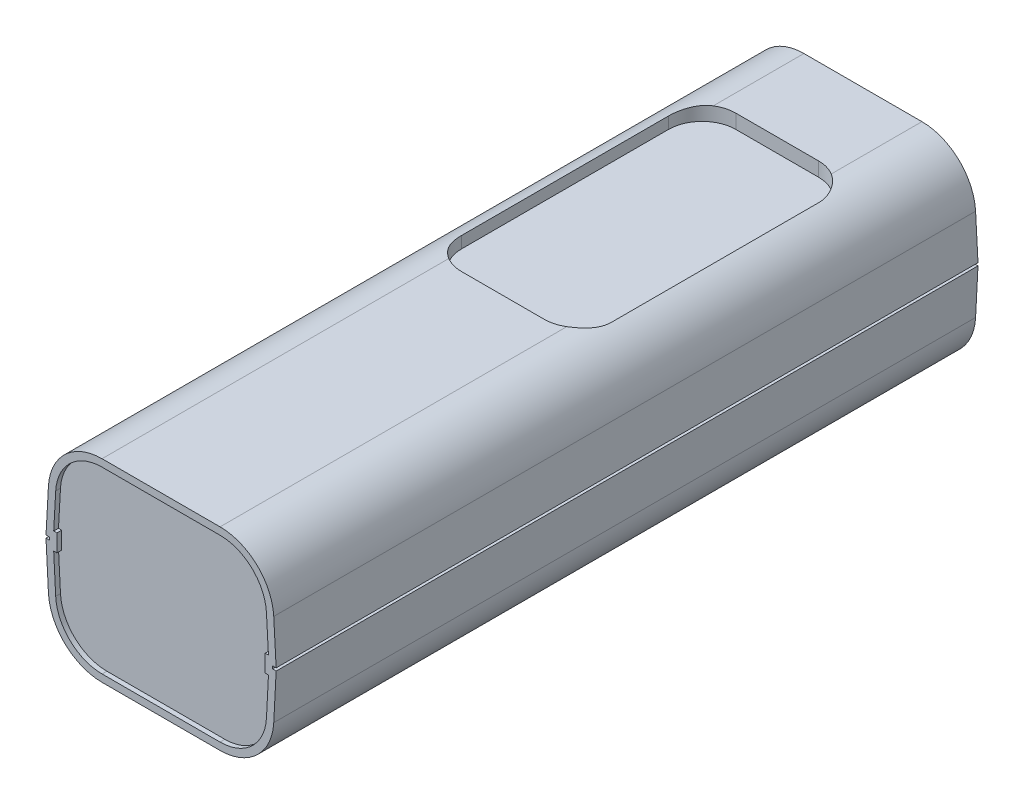
SolidWorks part; units mm, degrees
material "ABS"
ref_plane "Front Plane" through (0, 0, 0) normal (0, 0, 1) x (1, 0, 0)
ref_plane "Top Plane" through (0, 0, 0) normal (0, 1, 0) x (1, 0, 0)
ref_plane "Right Plane" through (0, 0, 0) normal (1, 0, 0) x (0, 0, -1)
sketch "main_features_sketch" plane through (0, 0, 0) normal (0, 0, 1) x (1, 0, 0)
  line L1 (12.9462, 21.25) -> (-12.9462, 21.25)
  line L3 (12.9462, -21.25) -> (-12.9462, -21.25)
  line L5 (0, -21.25) -> (0, 21.25) construction
  line L6 (25.25, 0) -> (-25.25, 0) construction
  line L7 (-25.25, 0) -> (-24.722, -10.0752)
  line L8 (-24.7199, 10.1141) -> (-25.25, 0.6)
  line L9 (-25.25, 0) -> (-24.45, 0)
  line L10 (-24.45, 0) -> (-24.45, 0.6)
  line L11 (-24.45, 0.6) -> (-25.25, 0.6)
  line L12 (25.25, 0) -> (24.45, 0)
  line L13 (24.45, 0.6) -> (25.25, 0.6)
  line L14 (24.45, 0) -> (24.45, 0.6)
  line L15 (24.7199, 10.1141) -> (25.25, 0.6)
  line L16 (25.25, 0) -> (24.722, -10.0752)
  line L17 (-12.9462, 9.4581) -> (0, 0) construction
  line L18 (0, 0) -> (-12.9462, -9.4581) construction
  line L19 (12.9462, 19.65) -> (-12.9462, 19.65)
  line L20 (23.1224, 10.0251) -> (23.5584, 2.2)
  line L21 (22.85, 2.2) -> (23.5584, 2.2)
  line L22 (22.85, -1.6) -> (22.85, 2.2)
  line L23 (23.564, -1.6) -> (22.85, -1.6)
  line L24 (23.564, -1.6) -> (23.1242, -9.9915)
  line L25 (12.9462, -19.65) -> (-12.9462, -19.65)
  line L26 (-23.564, -1.6) -> (-23.1242, -9.9915)
  line L27 (-23.564, -1.6) -> (-22.85, -1.6)
  line L28 (-22.85, -1.6) -> (-22.85, 2.2)
  line L29 (-22.85, 2.2) -> (-23.5584, 2.2)
  line L30 (-23.1224, 10.0251) -> (-23.5584, 2.2)
  arc A4 (-24.7199, 10.1141) -> (-12.9462, 21.25) centre (-12.9462, 9.4581) cw
  arc A5 (-24.722, -10.0752) -> (-12.9462, -21.25) centre (-12.9462, -9.4581) ccw
  arc A6 (24.7199, 10.1141) -> (12.9462, 21.25) centre (12.9462, 9.4581) ccw
  arc A7 (24.722, -10.0752) -> (12.9462, -21.25) centre (12.9462, -9.4581) cw
  arc A8 (-23.1224, 10.0251) -> (-12.9462, 19.65) centre (-12.9462, 9.4581) cw
  arc A9 (23.1224, 10.0251) -> (12.9462, 19.65) centre (12.9462, 9.4581) ccw
  arc A10 (23.1242, -9.9915) -> (12.9462, -19.65) centre (12.9462, -9.4581) cw
  arc A11 (-23.1242, -9.9915) -> (-12.9462, -19.65) centre (-12.9462, -9.4581) ccw
  point P0 (0, 0)
  point P1 (-23.6809, -0.3547)
  point P3 (-23.6369, -0.2077)
  point P44 (-23.6478, 0)
  dimension "D1" = 0.6
  dimension "D5" = 55.65
  dimension "D2" = 0.8
  dimension "D3" = 50.5
  dimension "D4" = 42.5
  dimension "D6" = 87
  dimension "D7" = 1.6
extrude "main_body" add sketch "main_features_sketch" along normal mid plane 154 contours L26 A11 L25 A10 L24 L23 L22 L21 L20 A9 L19 A8 L30 L29 L28 L27 | A7 L16 L12 L14 L13 L15 A6 L1 A4 L8 L11 L10 L9 L7 A5 L3 A11 L26 L27 L28 L29 L30 A8 L19 A9 L20 L21 L22 L23 L24 A10 L25 region at (20.5956, 17.5455, 0) region at (0, -0.0004, 0)
sketch "lens_sketch" plane through (0, 21.25, 0) normal (0, 1, 0) x (1, 0, 0)
  line L0 (0, 77) -> (0, -77) construction
  line L3 (12.9462, 77) -> (-12.9462, 77) construction
  line L4 (9.0857, 58.2) -> (-9.0857, 58.2)
  line L5 (16.475, 50.8107) -> (16.475, 5.3893)
  line L6 (9.0857, -2) -> (-9.0857, -2)
  line L7 (-16.475, 50.8107) -> (-16.475, 5.3893)
  line L8 (0, -2) -> (0, 58.2) construction
  line L9 (16.475, 28.1) -> (-16.475, 28.1) construction
  line L10 (12.9462, -77) -> (-12.9462, -77) construction
  arc A0 (16.475, 5.3893) -> (9.0857, -2) centre (9.0857, 5.3893) cw
  arc A1 (-9.0857, -2) -> (-16.475, 5.3893) centre (-9.0857, 5.3893) cw
  arc A2 (9.0857, 58.2) -> (16.475, 50.8107) centre (9.0857, 50.8107) cw
  arc A3 (-9.0857, 58.2) -> (-16.475, 50.8107) centre (-9.0857, 50.8107) ccw
  point P2 (0, 77)
  point P6 (0, -77)
  point P8 (0, 28.1)
  point P20 (-10.0055, 25.8209)
  point P21 (0, 0)
  point P23 (0, 0)
  point P25 (0, 29.6793)
  point P26 (-16.475, 6.0775)
  dimension "D1" = 63.7
  dimension "D2" = 60.2
  dimension "D3" = 32.95
  dimension "D4" = 18.8
extrude "lens_cut" cut sketch "lens_sketch" against normal blind 3.1
extrude "end_recess" cut sketch "Sketch1<3>" along normal blind 1.05 from surface contours L26 A11 L25 A10 L24 L23 L22 L21 L20 A9 L19 A8 L30 L29 L28 L27 region at (0, -0.0004, 0) starting at face at (0, 0.1541, -77)
sketch "Sketch1<3>" plane through (0, 0, 0) normal (0, 0, 1) x (1, 0, 0) same geometry as "main_features_sketch"
mirror "end_recess_2" about plane through (0, 0, 0) normal (0, 0, 1) of "end_recess"
ref_axis "emitting_axis" through (0, 21.25, -28.1) along (0, 1, 0)
ref_plane "emitting_plane" through (0, 18.15, 0) normal (0, 1, 0) x (1, 0, 0)
